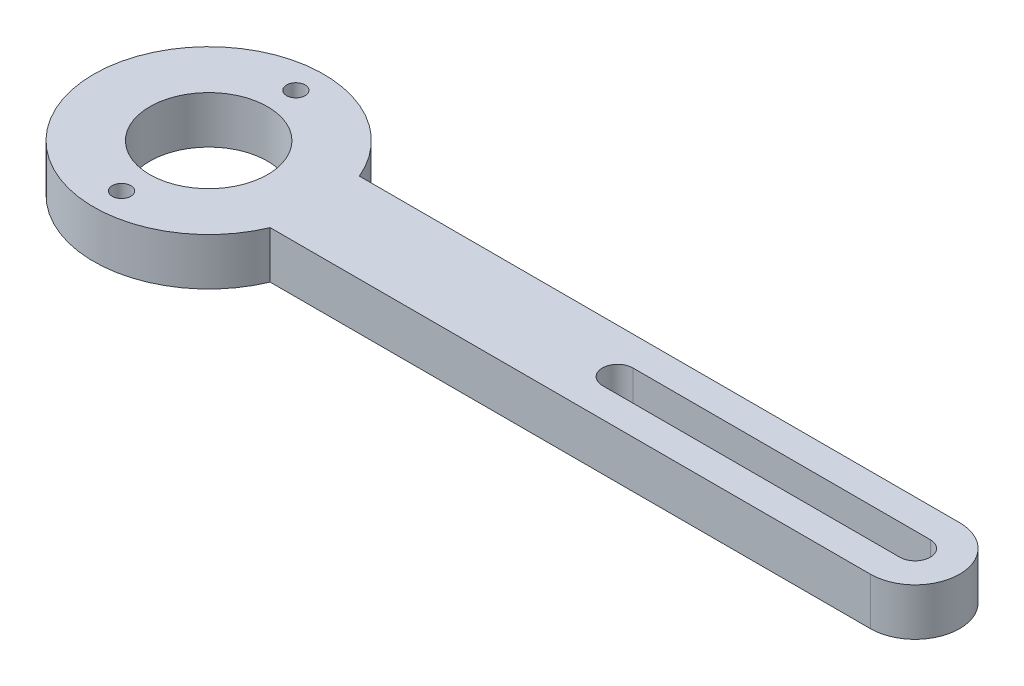
SolidWorks part; units mm, degrees
ref_plane "Front Plane" through (0, 0, 0) normal (0, 0, 1) x (1, 0, 0)
ref_plane "Top Plane" through (0, 0, 0) normal (0, 1, 0) x (1, 0, 0)
ref_plane "Right Plane" through (0, 0, 0) normal (1, 0, 0) x (0, 0, -1)
sketch "Sketch1" plane through (0, 0, 0) normal (0, 1, 0) x (1, 0, 0)
  line L0 (0, 0) -> (100, 0) construction
  line L1 (14.2645, 6) -> (95, 6)
  line L3 (95, -6) -> (14.2645, -6)
  line L4 (55, 0) -> (95, 0) construction
  line L5 (55, 2.05) -> (95, 2.05)
  line L6 (55, -2.05) -> (95, -2.05)
  line L7 (95, 6) -> (95, -6) construction
  arc A0 (14.2645, 6) -> (14.2645, -6) centre (0, 0) ccw
  circle A1 centre (0, 0) radius 7.92
  arc A2 (14.2645, -6) -> (14.2645, 6) centre (0, 0) ccw construction
  arc A3 (55, 2.05) -> (55, -2.05) centre (55, 0) ccw
  arc A4 (95, -2.05) -> (95, 2.05) centre (95, 0) ccw
  circle A5 centre (0, 0) radius 11.725 construction
  circle A6 centre (0, -11.725) radius 1.25
  circle A7 centre (0, 11.725) radius 1.25
  arc A8 (95, -6) -> (95, 6) centre (95, 0) ccw
  point P11 (75, 0)
  dimension "D1" = 15.84
  dimension "D2" = 30.95
  dimension "D5" = 4.1
  dimension "D8" = 7.555
  dimension "D9" = 23.45
  dimension "D10" = 2.5
  dimension "D3" = 12
  dimension "D4" = 95
  dimension "D6" = 40
  dimension "D7" = 5
extrude "Boss-Extrude1" add sketch "Sketch1" along normal blind 6.35
